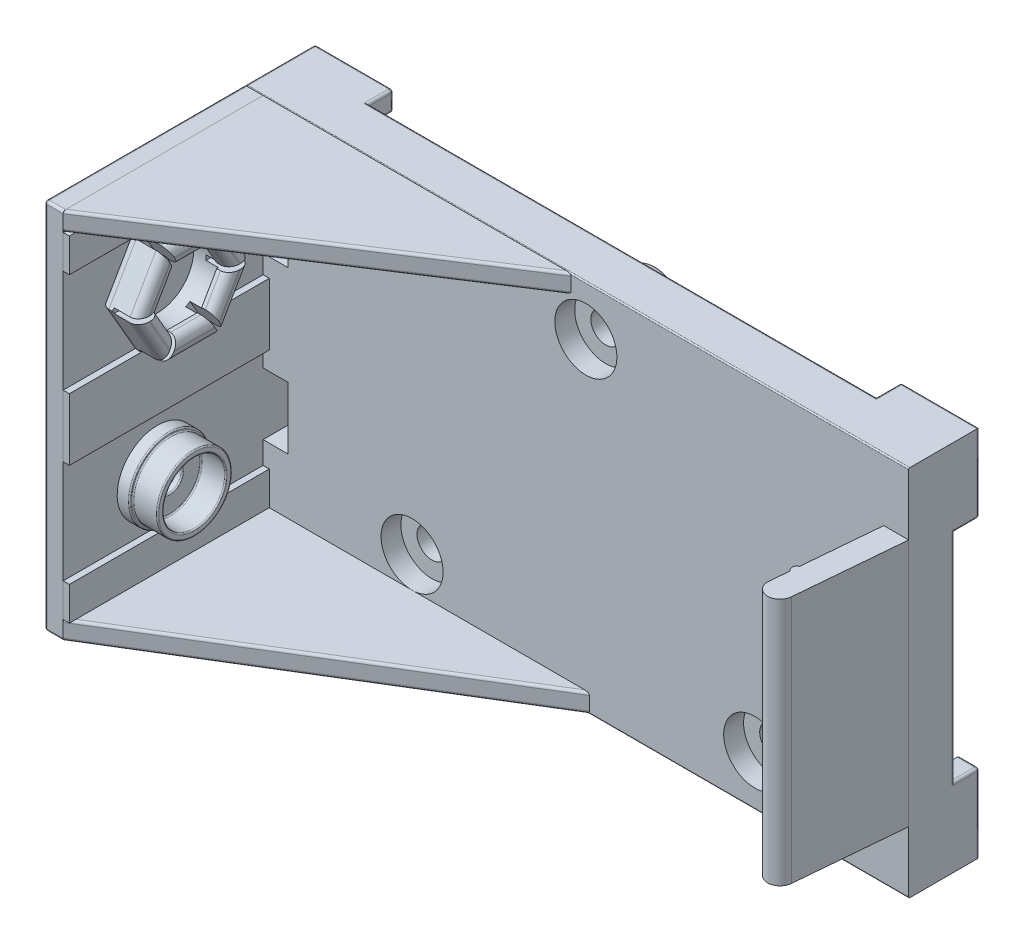
SolidWorks part; units mm, degrees
ref_plane "Ön Düzlem" through (0, 0, 0) normal (0, 0, 1) x (1, 0, 0)
ref_plane "Üst Düzlem" through (0, 0, 0) normal (0, 1, 0) x (1, 0, 0)
ref_plane "Sağ Düzlem" through (0, 0, 0) normal (1, 0, 0) x (0, 0, -1)
sketch "Çizim3" plane through (0, 0, 0) normal (0, 0, 1) x (1, 0, 0)
  line L1 (0, 0) -> (53.5, 0)
  line L2 (0, 0) -> (0, 30)
  line L3 (0, 30) -> (53.5, 30)
  line L4 (53.5, 0) -> (53.5, 30)
  dimension "D1" = 53.5
  dimension "D2" = 30
extrude "Yükseklik-Ekstrüzyon1" add sketch "Çizim3" along normal blind 3.7
sketch "Çizim4" plane through (0, 0, 0) normal (0, 0, -1) x (-1, 0, 0)
  line L0 (-53.5, 0) -> (-53.5, 6.3)
  line L1 (-53.5, 0) -> (-53.5, 30) construction
  line L2 (-53.5, 6.3) -> (-51.9, 6.3)
  line L3 (-51.9, 6.3) -> (-51.9, 1.6)
  line L4 (-51.9, 1.6) -> (-47.2, 1.6)
  line L5 (-47.2, 1.6) -> (-47.2, 0)
  line L6 (0, 0) -> (-53.5, 0) construction
  line L7 (-47.2, 0) -> (-53.5, 0)
  line L8 (-53.5, 0) -> (-53.8696, -0.1083)
  line L9 (-53.5, 15) -> (0, 15) construction
  line L10 (0, 30) -> (0, 0) construction
  line L11 (-26.75, 30) -> (-26.75, 0) construction
  line L12 (-53.5, 30) -> (0, 30) construction
  line L13 (-53.5, 30) -> (-53.8696, 30.1083)
  line L14 (-47.2, 30) -> (-53.5, 30)
  line L15 (-47.2, 28.4) -> (-47.2, 30)
  line L16 (-51.9, 28.4) -> (-47.2, 28.4)
  line L17 (-51.9, 23.7) -> (-51.9, 28.4)
  line L18 (-53.5, 23.7) -> (-51.9, 23.7)
  line L19 (-53.5, 30) -> (-53.5, 23.7)
  line L20 (0, 30) -> (0, 23.7)
  line L21 (0, 23.7) -> (-1.6, 23.7)
  line L22 (-1.6, 23.7) -> (-1.6, 28.4)
  line L23 (-1.6, 28.4) -> (-6.3, 28.4)
  line L24 (-6.3, 28.4) -> (-6.3, 30)
  line L25 (-6.3, 30) -> (0, 30)
  line L26 (0, 30) -> (0.3696, 30.1083)
  line L27 (0, 0) -> (0.3696, -0.1083)
  line L28 (-6.3, 0) -> (0, 0)
  line L29 (-6.3, 1.6) -> (-6.3, 0)
  line L30 (-1.6, 1.6) -> (-6.3, 1.6)
  line L31 (-1.6, 6.3) -> (-1.6, 1.6)
  line L32 (0, 6.3) -> (-1.6, 6.3)
  line L33 (0, 0) -> (0, 6.3)
  line M7 (0, 0) -> (0, 30)
  line M9 (-53.5, 30) -> (-53.5, 0)
  line M10 (-53.5, 0) -> (0, 0)
  dimension "D1" = 6.3
  dimension "D2" = 6.3
  dimension "D3" = 1.6
  dimension "D4" = 1.6
extrude "Yükseklik-Ekstrüzyon2" add sketch "Çizim4" along normal blind 2 contours L5 L4 L3 L2 M9 M10 | L32 L31 L30 L29 M7 M10 | L19 L18 L17 L16 L15 L14 | L20 L21 L22 L23 L24 L25 region at (6.2109, 0.8, 0) region at (53.4109, 3.15, 0)
sketch "Çizim5" plane through (0, 0, 3.7) normal (0, 0, 1) x (1, 0, 0)
  line L0 (0, 0) -> (53.5, 0) construction
  line L1 (0, 30) -> (1.5, 30)
  line L2 (0, 30) -> (0, 0)
  line L3 (0, 0) -> (1.5, 0)
  line L4 (1.5, 30) -> (1.5, 0)
  dimension "D1" = 1.5
extrude "Yükseklik-Ekstrüzyon3" add sketch "Çizim5" along normal blind 16.1 separate body
sketch "Çizim6" plane through (0, 30, 0) normal (0, 1, 0) x (1, 0, 0)
  line L0 (1.5, -19.8) -> (26.3, -3.7)
  line L1 (26.3, -3.7) -> (1.5, -3.7)
  line L2 (1.5, -3.7) -> (1.5, -19.8)
  dimension "D1" = 26.3
extrude "Yükseklik-Ekstrüzyon4" add sketch "Çizim6" against normal blind 1.5 separate body
sketch "Çizim7" plane through (0, 0, 0) normal (0, -1, 0) x (1, 0, 0)
  line L0 (1.5, 19.8) -> (27.8, 3.7)
  line L1 (0, 3.7) -> (53.5, 3.7) construction
  line L2 (27.8, 3.7) -> (1.5, 3.7)
  line L3 (1.5, 3.7) -> (1.5, 19.8)
  dimension "D1" = 26.3
extrude "Yükseklik-Ekstrüzyon6" add sketch "Çizim7" against normal blind 1.5 separate body
sketch "Çizim8" plane through (0, 0, 0) normal (0, -1, 0) x (1, 0, 0)
  line L0 (53.5, 3.7) -> (52.7396, 12.391)
  line L1 (50.9471, 9.9328) -> (51.4924, 3.7)
  line L2 (50.7473, 12.2166) -> (50.8857, 10.6341)
  line L3 (0, 3.7) -> (53.5, 3.7) construction
  line L4 (51.4924, 3.7) -> (53.5, 3.7)
  line L5 (6.3, 0) -> (47.2, 0) construction
  arc A0 (50.7473, 12.2166) -> (52.7396, 12.391) centre (51.7434, 12.3038) cw
  arc A1 (50.8857, 10.6341) -> (50.9471, 9.9328) centre (51.1057, 10.3) ccw
  point P8 (51.6563, 13.3)
  dimension "D4" = 1
  dimension "D6" = 0.8
  dimension "D1" = 13.3
  dimension "D2" = 85
  dimension "D3" = 2
  dimension "D5" = 0.19
  dimension "D7" = 3
extrude "Yükseklik-Ekstrüzyon9" add sketch "Çizim8" against normal blind 30
sketch "Çizim9" plane through (53.5, 0, 0) normal (1, 0, 0) x (0, 0, -1)
  line L1 (-3.7, 0) -> (-14.3628, 0)
  line L2 (-3.7, 0) -> (-3.7, 5)
  line L3 (-3.7, 5) -> (-14.3628, 5)
  line L4 (-14.3628, 0) -> (-14.3628, 5)
  line L5 (-3.7, 30) -> (-15.1077, 30)
  line L6 (-3.7, 30) -> (-3.7, 25)
  line L7 (-3.7, 25) -> (-15.1077, 25)
  line L8 (-15.1077, 30) -> (-15.1077, 25)
  dimension "D1" = 5
  dimension "D2" = 5
extrude "Kes-Ekstrüzyon1" cut sketch "Çizim9" against normal blind 10
sketch "Çizim10" plane through (0, 0, 0) normal (-1, 0, 0) x (0, 0, 1)
  line L0 (12.2, 37.8998) -> (12.2, -4.8052) construction
  line L1 (19.8, 30) -> (19.8, 0) construction
  line L2 (25.8757, 8) -> (-4.2751, 8) construction
  line L3 (25.8757, 22) -> (-5.0655, 22) construction
  line L4 (19.8, 0) -> (3.7, 0) construction
  line L5 (19.8, 30) -> (3.7, 30) construction
  circle A0 centre (12.2, 8) radius 3.8
  circle A1 centre (12.2, 22) radius 3.8
  point P18 (13.7129, 22)
  point P19 (17.3254, 16.7988)
  dimension "D3" = 7.6
  dimension "D4" = 7.6
  dimension "D1" = 7.6
  dimension "D2" = 8
  dimension "D5" = 8
extrude "Kes-Ekstrüzyon2" cut sketch "Çizim10" against normal blind 0.5
sketch "Çizim11" plane through (0.5, 0, 0) normal (-1, 0, 0) x (0, 0, 1)
  circle A0 centre (12.2, 8) radius 1
  circle A1 centre (12.2, 22) radius 1
  dimension "D1" = 2
  dimension "D2" = 2
extrude "Kes-Ekstrüzyon3" cut sketch "Çizim11" against normal blind 3
hole_wizard "M2 Yassı Başlı Makine Vidası İçin Havşa1" positions "Çizim13" profile "Çizim12" counterbore size "M2" standard "ANSI Metrik" end condition through all
sketch "Çizim13" plane through (0, 0, 3.7) normal (0, 0, 1) x (1, 0, 0)
  line L0 (53.5, 25) -> (53.5, 30) construction
  line L1 (53.5, 30) -> (0, 30) construction
  line L2 (53.5, 0) -> (53.5, 5) construction
  line L3 (0, 0) -> (53.5, 0) construction
  line L4 (1.5, 0) -> (27.8, 0) construction
  point P0 (27.5, 26)
  point P2 (41.1, 4)
  point P4 (13.5, 4)
  dimension "D1" = 26
  dimension "D2" = 4
  dimension "D3" = 12.4
  dimension "D4" = 4
  dimension "D5" = 40
  dimension "D6" = 4
sketch "Çizim12" plane through (27.5, 26, 3.7) normal (1, 0, 0) x (0, -1, 0)
  line L0 (0, 0) -> (0, 5.7)
  line L1 (0, 5.7) -> (1.2, 5.7)
  line L3 (1.2, 5.7) -> (1.2, 1.6)
  line L4 (1.2, 1.6) -> (2.5, 1.6)
  line L5 (2.5, 1.6) -> (2.5, 0)
  line L7 (2.5, 0) -> (0, 0)
  line L11 (0, -6.35) -> (0, 107.95) construction
  dimension "Thru Hole Dia." = 2.4
  dimension "Thru Hole Depth" = 5.7
  dimension "C'Bore Dia." = 5
  dimension "C'Bore Depth" = 1.6
sketch "Çizim14" plane through (0, 0, 0) normal (0, 0, -1) x (-1, 0, 0)
  circle A0 centre (-27.5, 26) radius 1.2
  circle A1 centre (-27.5, 26) radius 2.4
  circle A2 centre (-41.1, 4) radius 2.4
  circle A3 centre (-41.1, 4) radius 1.2
  circle A4 centre (-13.5, 4) radius 2.4
  circle A5 centre (-13.5, 4) radius 1.2
  dimension "D1" = 1.2
  dimension "D2" = 1.2
  dimension "D3" = 1.2
extrude "Yükseklik-Ekstrüzyon10" add sketch "Çizim14" along normal blind 2
fillet "Radyus2" radius 0.5 3 edges at (25.1, 26, -2) (11.1, 4, -2) (38.7, 4, -2)
sketch "Çizim16" plane through (0, 0, 19.8) normal (0, 0, 1) x (1, 0, 0)
  line L0 (1.5, 15) -> (1.5, 12.5)
  line L1 (1.5, 0) -> (1.5, 30) construction
  line L2 (1.5, 12.5) -> (2, 12.5)
  line L3 (2, 12.5) -> (2, 17.5)
  line L4 (2, 17.5) -> (1.5, 17.5)
  line L5 (1.5, 17.5) -> (1.5, 15)
  dimension "D1" = 2.5
  dimension "D2" = 2.5
  dimension "D3" = 0.5
extrude "Yükseklik-Ekstrüzyon13" add sketch "Çizim16" against normal blind 16.1 separate body
sketch "Çizim17" plane through (0, 0, 19.8) normal (0, 0, 1) x (1, 0, 0)
  line L0 (0, 0) -> (1.5, 0) construction
  line L1 (1.5, 1.5) -> (2, 1.5)
  line L2 (1.5, 1.5) -> (1.5, 4.2)
  line L3 (1.5, 4.2) -> (2, 4.2)
  line L4 (2, 1.5) -> (2, 4.2)
  line L6 (1.5, 30) -> (0, 30) construction
  line L7 (1.5, 28.5) -> (2, 28.5)
  line L8 (1.5, 28.5) -> (1.5, 25.8)
  line L9 (1.5, 25.8) -> (2, 25.8)
  line L10 (2, 28.5) -> (2, 25.8)
  dimension "D1" = 4.2
  dimension "D2" = 0.5
  dimension "D3" = 4.2
  dimension "D4" = 0.5
extrude "Yükseklik-Ekstrüzyon16" add sketch "Çizim17" against normal blind 16.1 separate body
sketch "Çizim18" plane through (1.5, 0, 0) normal (1, 0, 0) x (0, 0, -1)
  circle A0 centre (-12.2, 8) radius 3.25
  dimension "D1" = 6.5
extrude "Yükseklik-Ekstrüzyon17" add sketch "Çizim18" along normal blind 1 separate body
sketch "Çizim19" plane through (2.5, 0, 0) normal (1, 0, 0) x (0, 0, -1)
  circle A0 centre (-12.2, 8) radius 3
  circle A1 centre (-12.2, 8) radius 2.5
  dimension "D1" = 6
  dimension "D2" = 0.5
extrude "Yükseklik-Ekstrüzyon19" add sketch "Çizim19" along normal blind 2
sketch "Çizim20" plane through (0.5, 0, 0) normal (-1, 0, 0) x (0, 0, 1)
  circle A0 centre (12.2, 8) radius 1
extrude "Kes-Ekstrüzyon4" cut sketch "Çizim20" against normal blind 4
fillet "Radyus3" radius 0.1 6 edges at (2.5, 11.25, 12.2) (2.5, 11, 12.2) (2.5, 9, 12.2) (2.5, 10.5, 12.2) (4.5, 11, 12.2) (4.5, 10.5, 12.2)
sketch "Çizim22" plane through (0, 0, 3.7) normal (0, 0, 1) x (1, 0, 0)
  line L0 (1.5, 0) -> (1.5, 30) construction
  line L1 (1.5, 6) -> (3.5, 6)
  line L2 (1.5, 6) -> (1.5, 11)
  line L3 (1.5, 11) -> (3.5, 11)
  line L4 (3.5, 6) -> (3.5, 11)
  line L5 (1.5, 0) -> (27.8, 0) construction
  line L6 (1.5, 19) -> (3.5, 19)
  line L7 (1.5, 19) -> (1.5, 24)
  line L8 (1.5, 24) -> (3.5, 24)
  line L9 (3.5, 19) -> (3.5, 24)
  line L10 (53.5, 30) -> (0, 30) construction
  dimension "D1" = 5
  dimension "D2" = 5
  dimension "D3" = 2
  dimension "D4" = 2
  dimension "D5" = 11
  dimension "D6" = 11
extrude "Kes-Ekstrüzyon5" cut sketch "Çizim22" against normal blind 4
sketch "Çizim23" plane through (1.5, 0, 0) normal (1, 0, 0) x (0, 0, -1)
  line L1 (-7.5812, 22) -> (-9.8906, 26)
  line L2 (-9.8906, 26) -> (-14.5094, 26)
  line L3 (-14.5094, 26) -> (-16.8188, 22)
  line L4 (-16.8188, 22) -> (-14.5094, 18)
  line L5 (-14.5094, 18) -> (-9.8906, 18)
  line L6 (-9.8906, 18) -> (-7.5812, 22)
  line L7 (-10.7566, 24.5) -> (-13.6434, 24.5)
  line L8 (-13.6434, 24.5) -> (-15.0868, 22)
  line L9 (-15.0868, 22) -> (-13.6434, 19.5)
  line L10 (-13.6434, 19.5) -> (-10.7566, 19.5)
  line L11 (-10.7566, 19.5) -> (-9.3132, 22)
  line L12 (-9.3132, 22) -> (-10.7566, 24.5)
  circle A0 centre (-12.2, 22) radius 4 construction
  circle A1 centre (-12.2, 22) radius 2.5 construction
  dimension "D1" = 8
  dimension "D2" = 1.5
extrude "Yükseklik-Ekstrüzyon20" add sketch "Çizim23" along normal blind 3 separate body
fillet "Radyus4" radius 0.7 18 edges at (1.5, 26, 12.2) (1.5, 24, 8.7359) (1.5, 20, 8.7359) (1.5, 18, 12.2) (1.5, 20, 15.6641) (1.5, 24, 15.6641) (4.5, 23.25, 14.3651) (4.5, 24.5, 12.2) (4.5, 23.25, 10.0349) (4.5, 20.75, 10.0349) (4.5, 19.5, 12.2) (4.5, 20.75, 14.3651) (4.5, 18, 12.2) (4.5, 20, 8.7359) (4.5, 24, 8.7359) (4.5, 26, 12.2) (4.5, 24, 15.6641) (4.5, 20, 15.6641)
sketch "Çizim24" plane through (1.5, 0, 0) normal (1, 0, 0) x (0, 0, -1)
  circle A0 centre (-12.2, 22) radius 2.1811
  circle A1 centre (-12.2, 22) radius 2.9076
extrude "Kes-Ekstrüzyon7" cut sketch "Çizim24" along normal blind 2
fillet "Radyus5" radius 0.2 2 edges at (13.9, 28.5, 11.75) (13.9, 30, 11.75)
fillet "Radyus6" radius 0.2 1 edges at (0, 15, 19.8)
fillet "Radyus7" radius 0.2 2 edges at (14.65, 0, 11.75) (14.65, 1.5, 11.75)
fillet "Radyus8" radius 0.2 3 edges at (0.85, 0, 19.8) (0.0586, 0, 19.7414) (0, 0, 11.65)
fillet "Radyus9" radius 0.2 1 edges at (0, 0, 0.85)
fillet "Radyus10" radius 0.2 3 edges at (0, 30, 11.65) (0.85, 30, 19.8) (0.0586, 30, 19.7414)
fillet "Radyus11" radius 0.2 1 edges at (0, 30, 0.85)
fillet "Radyus12" radius 0.2 41 edges at (3.25, 0, -2) (0.0586, 0.0586, -2) (0, 26.75, -2) (0.0586, 29.9414, -2) (47.2, 0.8, -2) (49.55, 1.6, -2) (52.7, 6.3, -2) (51.9, 3.95, -2) (47.2, 29.2, -2) (52.7, 23.7, -2) (51.9, 26.05, -2) (49.55, 28.4, -2) (1.6, 23.7, -1.15) (6.3, 28.4, -1) (6.3, 29.2, -2) (3.95, 28.4, -2) (0.8, 23.7, -2) (1.6, 26.05, -2) (6.3, 0.8, -2) (3.95, 1.6, -2) (1.6, 3.95, -2) (0.8, 6.3, -2) (0, 6.3, -1) (1.6, 6.3, -1.15) (0, 15, 0) (0, 23.7, -1) (47.2, 30, -1) (50.35, 30, -2) (53.5, 26.85, -2) (53.5, 23.7, -1) (53.5, 3.15, -2) (50.35, 0, -2) (6.3, 0, -1) (0, 3.25, -2) (3.25, 30, -2) (6.3, 30, -1) (26.75, 30, 0)
fillet "Radyus14" radius 0.1 5 edges at (0.0586, 29.9414, 3.7) (0, 15, 3.7) (0.0586, 0.0586, 3.7)
sketch "Çizim25" plane through (1.5, 0, 0) normal (1, 0, 0) x (0, 0, -1)
  circle A0 centre (-12.2, 22) radius 2.9938
  circle A1 centre (-12.2, 22) radius 1
  dimension "D1" = 2
extrude "Yükseklik-Ekstrüzyon22" add sketch "Çizim25" along normal blind 0.001
sketch "Çizim26" plane through (0.5, 0, 0) normal (-1, 0, 0) x (0, 0, 1)
  circle A0 centre (12.2, 22) radius 3.8
  circle A1 centre (12.2, 22) radius 1
extrude "Yükseklik-Ekstrüzyon23" add sketch "Çizim26" along normal blind 0.001
sketch "Çizim27" plane through (4.5, 0, 0) normal (1, 0, 0) x (0, 0, -1)
  line L0 (-13.6284, 24.0849) -> (-14.9454, 26.3659)
  line L1 (-17.7896, 21.7997) -> (-14.2943, 21.7997)
  line L2 (-17.7896, 21.7997) -> (-17.7896, 22.1997)
  line L3 (-17.7896, 22.1997) -> (-14.2943, 22.1997)
  line L4 (-14.2943, 21.7997) -> (-14.2943, 22.1997)
  line L5 (-14.9454, 26.3659) -> (-14.599, 26.5659)
  line L6 (-14.599, 26.5659) -> (-13.282, 24.2849)
  line L7 (-13.282, 24.2849) -> (-13.6284, 24.0849)
  line L8 (-13.6284, 24.0849) -> (-13.5756, 24.1497)
  line L9 (-11.2882, 23.9825) -> (-9.7997, 26.5607)
  line L10 (-9.7997, 26.5607) -> (-9.4533, 26.3607)
  line L11 (-9.4533, 26.3607) -> (-10.9418, 23.7825)
  line L12 (-10.9418, 23.7825) -> (-11.2882, 23.9825)
  line L13 (-14.1053, 18.7) -> (-14.5094, 18) construction
  line L14 (-10.5935, 21.7997) -> (-6.9508, 21.7997)
  line L15 (-6.9508, 21.7997) -> (-6.9508, 22.1997)
  line L16 (-6.9508, 22.1997) -> (-10.5935, 22.1997)
  line L17 (-10.5935, 22.1997) -> (-10.5935, 21.7997)
  line L18 (-9.6044, 17.8856) -> (-11.0614, 20.4093)
  line L19 (-11.0614, 20.4093) -> (-11.4079, 20.2093)
  line L20 (-11.4079, 20.2093) -> (-9.9508, 17.6856)
  line L21 (-9.9508, 17.6856) -> (-9.6044, 17.8856)
  line L22 (-15.1807, 17.2979) -> (-14.8342, 17.0979)
  line L23 (-14.8342, 17.0979) -> (-12.9555, 20.352)
  line L24 (-12.9555, 20.352) -> (-13.3019, 20.552)
  line L25 (-13.3019, 20.552) -> (-15.1807, 17.2979)
  line L26 (-16.0105, 22) -> (-16.8188, 22) construction
  line L27 (-14.1053, 25.3) -> (-14.5094, 26) construction
  line L28 (-9.8906, 26) -> (-10.2947, 25.3) construction
  line L29 (-9.3132, 22) -> (-8.505, 22) construction
  line L30 (-9.8906, 18) -> (-10.2947, 18.7) construction
  line M15 (-14.0475, 18.8) -> (-15.895, 22)
  line M16 (-15.895, 22) -> (-14.0475, 25.2)
  line M17 (-14.0475, 25.2) -> (-10.3525, 25.2)
  line M18 (-10.3525, 25.2) -> (-8.505, 22)
  line M19 (-8.505, 22) -> (-10.3525, 18.8)
  line M20 (-10.3525, 18.8) -> (-14.0475, 18.8)
  line M21 (-16.0105, 22) -> (-14.1053, 18.7)
  line M22 (-14.1053, 18.7) -> (-10.2947, 18.7)
  line M23 (-10.2947, 18.7) -> (-8.3895, 22)
  line M24 (-8.3895, 22) -> (-10.2947, 25.3)
  line M25 (-10.2947, 25.3) -> (-14.1053, 25.3)
  line M26 (-14.1053, 25.3) -> (-16.0105, 22)
  dimension "D1" = 0.4
  dimension "D2" = 0.4
  dimension "D3" = 0.4
  dimension "D4" = 0.4
  dimension "D5" = 0.4
extrude "Kes-Ekstrüzyon10" cut sketch "Çizim27" against normal blind 2 contours L24 L25 L23 M15 M20 | L3 L2 L1 M21 M26 | L1 L4 L3 M16 M15 | L11 L10 L9 M25 M24 | L16 L17 L14 M19 M18 | L15 L16 L14 M24 M23 | L3 L1 M26 M21 M15 M16 | L25 L23 M15 M21 M22 M20 | L11 L9 M24 M25 M17 M18 | L12 L11 L9 M18 M17 | L20 L21 L18 M23 M22 | L16 L14 M24 M18 M19 M23 | L25 L22 L23 M21 M22 | L19 L20 L18 M20 M19 | L20 L18 M20 M22 M23 M19 | L0 L5 L6 L7 | L12 L9 L10 L11 | L18 L19 L20 L21 | L1 L4 L3 L2 region at (4.5, 21.9997, 15.895) region at (4.5, 21.9997, 15.0661) region at (4.5, 21.9997, 16.8709) region at (4.5, 24.517, 10.7486) region at (4.5, 25.2008, 10.3539) region at (4.5, 25.8555, 9.976) region at (4.5, 18.8163, 14.0731) region at (4.5, 19.6584, 13.5858) region at (4.5, 17.9829, 14.5554) region at (4.5, 21.9997, 9.5778) region at (4.5, 21.9997, 8.505) region at (4.5, 21.9997, 7.6994) region at (4.5, 18.7954, 10.3606) region at (4.5, 19.5772, 10.8116) region at (4.5, 18.2657, 10.0554)
sketch "Çizim28" plane through (0.499, 0, 0) normal (-1, 0, 0) x (0, 0, 1)
  line L0 (13.066, 21.5) -> (12.2, 21)
  line L1 (13.066, 22.5) -> (14.5098, 22.5)
  line L2 (13.066, 22.5) -> (13.066, 21.5)
  line L3 (13.066, 21.5) -> (14.5098, 21.5)
  line L4 (14.5098, 22.5) -> (14.5098, 21.5)
  line L5 (13.066, 21.5) -> (13.7879, 20.2496)
  line L6 (12.2, 21) -> (12.9219, 19.7496)
  line L7 (13.7879, 20.2496) -> (12.9219, 19.7496)
  line L8 (12.2, 21) -> (11.334, 21.5)
  line L9 (12.2, 21) -> (11.4781, 19.7496)
  line L10 (11.334, 21.5) -> (10.6121, 20.2496)
  line L11 (11.4781, 19.7496) -> (10.6121, 20.2496)
  line L12 (11.334, 21.5) -> (11.334, 22.5)
  line L13 (11.334, 21.5) -> (9.8902, 21.5)
  line L14 (11.334, 22.5) -> (9.8902, 22.5)
  line L15 (9.8902, 21.5) -> (9.8902, 22.5)
  line L16 (11.334, 22.5) -> (12.2, 23)
  line L17 (11.334, 22.5) -> (10.6121, 23.7504)
  line L18 (12.2, 23) -> (11.4781, 24.2504)
  line L19 (10.6121, 23.7504) -> (11.4781, 24.2504)
  line L20 (12.2, 23) -> (13.066, 22.5)
  line L21 (12.2, 23) -> (12.9219, 24.2504)
  line L22 (13.066, 22.5) -> (13.7879, 23.7504)
  line L23 (12.9219, 24.2504) -> (13.7879, 23.7504)
  circle A0 centre (12.2, 22) radius 1 construction
  point P29 (12.2, 22)
  circle M3 centre (12.2, 22) radius 1
  dimension "D1" = 1
  dimension "D2" = 6
extrude "Yükseklik-Ekstrüzyon25" add sketch "Çizim28" against normal blind 1 and the other way blind 0.3 separate body contours L23 L21 L22 M3 | L19 L17 L18 M3 | L15 L13 L14 M3 | L11 L9 L10 M3 | L7 L5 L6 M3 | L4 L1 L3 M3 | L16 M3 | L8 M3 | L0 M3 | L2 M3 | L20 M3 | L12 L14 L15 L13 region at (0.499, 21.2033, 12.66) region at (0.499, 22, 13.8326) region at (0.499, 20.5861, 13.0163) region at (0.499, 22, 13.1199) region at (0.499, 21.2033, 11.74) region at (0.499, 20.5861, 11.3837) region at (0.499, 23.4139, 13.0163) region at (0.499, 22.7967, 12.66) region at (0.499, 22, 10.5674) region at (0.499, 23.4139, 11.3837) region at (0.499, 22.7967, 11.74)
fillet "Radyus16" radius 0.5 2 edges at (0.849, 21.5, 14.5098) (0.849, 22.5, 14.5098)
fillet "Radyus17" radius 0.5 2 edges at (0.849, 19.7496, 12.9219) (0.849, 20.2496, 13.7879)
fillet "Radyus18" radius 0.5 2 edges at (0.849, 20.2496, 10.6121) (0.849, 19.7496, 11.4781)
fillet "Radyus19" radius 0.5 2 edges at (0.849, 22.5, 9.8902) (0.849, 21.5, 9.8902)
fillet "Radyus20" radius 0.5 2 edges at (0.849, 24.2504, 11.4781) (0.849, 23.7504, 10.6121)
fillet "Radyus21" radius 0.5 2 edges at (0.849, 23.7504, 13.7879) (0.849, 24.2504, 12.9219)
sketch "Çizim29" plane through (0.5, 0, 0) normal (-1, 0, 0) x (0, 0, 1)
  line L0 (13.0617, 7.4904) -> (12.1957, 6.9904)
  line L1 (13.0596, 8.4904) -> (14.5055, 8.4904)
  line L2 (13.0596, 8.4904) -> (13.0596, 7.4904)
  line L3 (13.0596, 7.4904) -> (14.5055, 7.4904)
  line L4 (14.5055, 8.4904) -> (14.5055, 7.4904)
  line L5 (13.0617, 7.4904) -> (13.7836, 6.2401)
  line L6 (12.1957, 6.9904) -> (12.9176, 5.7401)
  line L7 (13.7836, 6.2401) -> (12.9176, 5.7401)
  line L8 (12.1957, 6.9904) -> (11.3297, 7.4904)
  line L9 (12.1957, 6.9904) -> (11.4738, 5.7401)
  line L10 (11.3297, 7.4904) -> (10.6078, 6.2401)
  line L11 (11.4738, 5.7401) -> (10.6078, 6.2401)
  line L12 (11.3297, 7.4904) -> (11.3297, 8.4904)
  line L13 (11.3297, 7.4904) -> (9.8859, 7.4904)
  line L14 (11.3297, 8.4904) -> (9.8859, 8.4904)
  line L15 (9.8859, 7.4904) -> (9.8859, 8.4904)
  line L16 (11.3297, 8.4904) -> (12.1957, 8.9904)
  line L17 (11.3297, 8.4904) -> (10.6078, 9.7408)
  line L18 (12.1957, 8.9904) -> (11.4738, 10.2408)
  line L19 (10.6078, 9.7408) -> (11.4738, 10.2408)
  line L20 (12.1957, 8.9904) -> (13.0617, 8.4904)
  line L21 (12.1957, 8.9904) -> (12.9176, 10.2408)
  line L22 (13.0617, 8.4904) -> (13.7836, 9.7408)
  line L23 (12.9176, 10.2408) -> (13.7836, 9.7408)
  point P24 (12.1957, 7.9904)
  circle M3 centre (12.2, 8) radius 1
  dimension "D1" = 1
extrude "Yükseklik-Ekstrüzyon26" add sketch "Çizim29" along normal blind 0.3 and the other way blind 1.5 separate body contours L23 L21 L22 M3 | L4 L1 L3 M3 | L7 L5 L0 L6 M3 | L11 L9 L8 L10 M3 | L15 L13 L12 L14 M3 | L0 M3 | L8 M3 | L12 L14 M3 | L17 L19 L18 L16 | L20 L22 L23 L21 | L2 L3 L4 L1 region at (0.5, 6.5789, 13.0101) region at (0.5, 7.9898, 13.8305) region at (0.5, 7.2002, 12.6618) region at (0.5, 6.5809, 11.382) region at (0.5, 7.1979, 11.7369) region at (0.5, 9.4088, 13.0147) region at (0.5, 7.9898, 10.5652) region at (0.5, 8, 11.2775)
fillet "Radyus22" radius 0.5 2 edges at (1.1, 8.4904, 14.5055) (1.1, 7.4904, 14.5055)
fillet "Radyus23" radius 0.5 2 edges at (1.1, 10.2408, 12.9176) (1.1, 9.7408, 13.7836)
fillet "Radyus24" radius 0.5 2 edges at (1.1, 10.2408, 11.4738) (1.1, 9.7408, 10.6078)
fillet "Radyus25" radius 0.5 2 edges at (1.1, 7.4904, 9.8859) (1.1, 8.4904, 9.8859)
fillet "Radyus26" radius 0.5 2 edges at (1.1, 5.7401, 11.4738) (1.1, 6.2401, 10.6078)
fillet "Radyus27" radius 0.5 2 edges at (1.1, 6.2401, 13.7836) (1.1, 5.7401, 12.9176)
